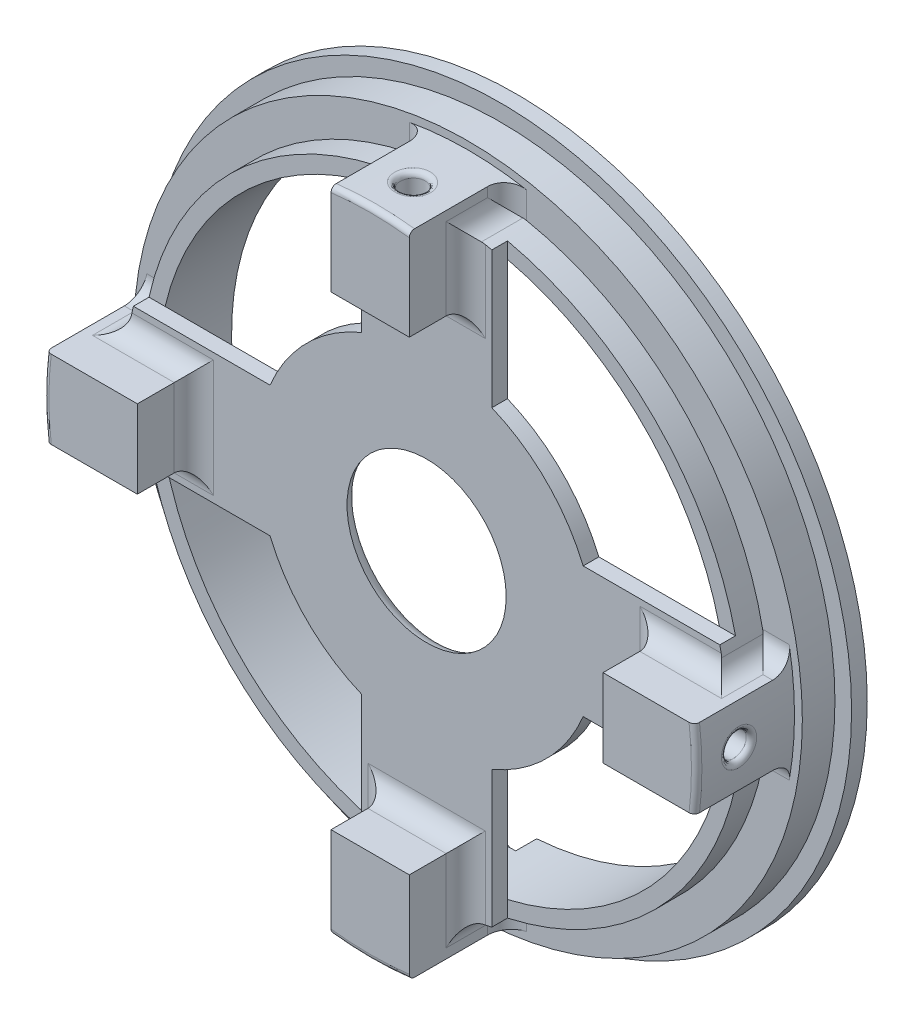
SolidWorks part; units mm, degrees
ref_plane "Front Plane" through (0, 0, 0) normal (0, 0, 1) x (1, 0, 0)
ref_plane "Top Plane" through (0, 0, 0) normal (0, 1, 0) x (1, 0, 0)
ref_plane "Right Plane" through (0, 0, 0) normal (1, 0, 0) x (0, 0, -1)
sketch "Sketch1" plane through (0, 0, 0) normal (0, 0, 1) x (1, 0, 0)
  circle A0 centre (0, 0) radius 53.8 construction
  circle A1 centre (0, 0) radius 53.8
  circle A4 centre (0, 0) radius 43.65
  circle A5 centre (0, 0) radius 43.65
  dimension "D1" = 0.65
extrude "Boss-Extrude1" add sketch "Sketch1" along normal blind 2.4
sketch "Sketch6" plane through (0, 0, 10.2) normal (0, 0, 1) x (1, 0, 0)
  circle A2 centre (0, 0) radius 43.65 construction
  circle A3 centre (0, 0) radius 43.65
extrude "Boss-Extrude4" add sketch "Sketch6" along normal blind 2.4 from offset 1.15 separate body
sketch "Sketch7" plane through (0, 0, 2.4) normal (0, 0, 1) x (1, 0, 0)
  circle A0 centre (0, 0) radius 43.65 construction
  circle A1 centre (0, 0) radius 43.65
extrude "Extrude-Thin2" add sketch "Sketch7" along normal up to surface (11.35 mm away) thin up to face at (43.65, 0, 13.75) thin type one direction wall 2.4
sketch "Sketch9" plane through (0, 0, 13.75) normal (0, 0, 1) x (1, 0, 0)
  circle A2 centre (0, 0) radius 12.2
  circle A3 centre (0, 0) radius 12.2
  dimension "D1" = 0.2
extrude "Cut-Extrude1" cut sketch "Sketch9" against normal up to surface (2.4 mm away) up to face at (43.65, 0, 11.35)
sketch "Sketch10" plane through (0, 0, 13.75) normal (0, 0, 1) x (1, 0, 0)
  line L0 (0, -46.05) -> (0, 46.05) construction
  line L1 (46.05, 0) -> (-46.05, 0) construction
  line L2 (10, -44.9511) -> (10, 44.9511)
  line L3 (44.9511, -10) -> (-44.9511, -10)
  line L4 (44.9511, 10) -> (-44.9511, 10)
  line L5 (-10, -44.9511) -> (-10, 44.9511)
  circle A0 centre (0, 0) radius 46.05 construction
  circle A1 centre (0, 0) radius 46.05
  circle A2 centre (0, 0) radius 26
  point P9 (10, 0)
  point P12 (0, -10)
  circle M7 centre (0, 0) radius 46.05
  dimension "D3" = 52
  dimension "D1" = 10
  dimension "D2" = 10
extrude "Cut-Extrude2" cut sketch "Sketch10" against normal up to surface (2.4 mm away) contours A2 L2 L3 M7 | A2 L3 L5 M7 | A2 L5 L4 M7 | A2 L4 L2 M7 region at (25.3451, -25.3451, 13.75) region at (-25.3451, -25.3451, 13.75) region at (-25.3451, 25.3451, 13.75) region at (25.3451, 25.3451, 13.75) up to face at (12.2, 0, 11.35)
sketch "Sketch8" plane through (0, 0, 2.4) normal (0, 0, 1) x (1, 0, 0)
  circle A2 centre (0, 0) radius 46.05 construction
  circle A3 centre (0, 0) radius 46.05
  circle A6 centre (0, 0) radius 51.25
  circle A7 centre (0, 0) radius 51.25
  dimension "D1" = 2.55
extrude "Boss-Extrude5" add sketch "Sketch8" along normal blind 5
sketch "Sketch12" plane through (0, 0, 7.4) normal (0, 0, 1) x (1, 0, 0)
  line L0 (0, 0) -> (-50.05, 0) construction
  line L1 (-49.6891, -6) -> (-35.6891, -6)
  line L2 (-35.6891, -6) -> (-35.6891, 6)
  line L3 (-49.6891, 6) -> (-35.6891, 6)
  circle A2 centre (0, 0) radius 50.05
  circle A3 centre (0, 0) radius 50.05
  point P8 (-35.6891, 0)
  circle M6 centre (0, 0) radius 46.05
  dimension "D2" = 6
  dimension "D3" = 14
  dimension "D1" = 1.2
extrude "Boss-Extrude6" add sketch "Sketch12" along normal blind 15 contours L2 L0 L1 M6 | L0 L2 L3 M6 | L0 A3 L1 M6 | L0 L3 A3 M6 region at (-40.8049, -2.9808, 7.4) region at (-40.8049, 2.9808, 7.4) region at (-47.9244, -3.0039, 7.4) region at (-47.9244, 3.0039, 7.4)
sketch "Sketch14" plane through (0, 0, 7.4) normal (0, 0, -1) x (-1, 0, 0)
  line L3 (43.2357, 6) -> (35.6891, 6)
  line L4 (35.6891, 6) -> (35.6891, -6)
  line L5 (35.6891, -6) -> (43.2357, -6)
  line L6 (43.2357, 6) -> (35.6891, 6)
  line L7 (35.6891, 6) -> (35.6891, -6)
  line L8 (35.6891, -6) -> (43.2357, -6)
  arc A1 (43.2357, -6) -> (43.2357, 6) centre (0, 0) ccw
  arc A2 (43.2357, -6) -> (43.2357, 6) centre (0, 0) ccw
  dimension "D1" = 0
extrude "Cut-Extrude4" cut sketch "Sketch14" against normal up to surface (3.95 mm away) up to face at (-7.8391, 0, 11.35)
sketch "Sketch13" plane through (-35.6891, 0, 0) normal (1, 0, 0) x (0, 0, -1)
  line L0 (-22.4, -6) -> (-22.4, 6) construction
  circle A0 centre (-15.9, 0) radius 1.9
  point P2 (-22.4, 0)
  dimension "D1" = 3.8
  dimension "D2" = 6.5
extrude "Cut-Extrude3" cut sketch "Sketch13" against normal through all from offset 5 offset against normal yes
fillet "Fillet1" radius 3 7 edges at (-35.6891, 0, 13.75) (-40.6733, -6, 13.75) (-45.6574, -6, 10.575) (-45.6574, 6, 10.575) (-40.6733, 6, 13.75) (-47.6733, -6, 7.4) (-47.6733, 6, 7.4)
fillet "Fillet2" radius 0.8 2 edges at (-50.05, 0, 22.4) (-50.0481, -0.4355, 17.7494)
pattern_circular "CirPattern4" count 4 over 360 about axis through (0, 0, 143.9991) along (0, 0, -1) of "Boss-Extrude6", "Cut-Extrude4", "Cut-Extrude3", "Fillet1", "Fillet2"
sketch "Sketch17" plane through (0, 0, 0) normal (0, 0, -1) x (-1, 0, 0)
  circle A0 centre (0, 0) radius 43.65 construction
  circle A1 centre (0, 0) radius 43.65
  ellipse E0 centre (0, 43) end of major axis (0, 39.2) minor radius 3 (2.9989, 42.8953) -> (-2.9989, 42.8953) ccw construction
  ellipse E1 centre (0, -43) end of major axis (0, -39.2) minor radius 3 (-2.9989, -42.8953) -> (2.9989, -42.8953) ccw construction
  ellipse E2 centre (0, 43) end of major axis (0, 39.2) minor radius 3 (2.9989, 42.8953) -> (-2.9989, 42.8953) ccw
  ellipse E3 centre (0, -43) end of major axis (0, -39.2) minor radius 3 (-2.9989, -42.8953) -> (2.9989, -42.8953) ccw
  spline S0 degree 1 poles (-3.1488, -42.892) (3.1488, -42.892) knots 0 0 1 1 construction
  spline S1 degree 3 poles (-3.1488, -42.892) (-3.1601, -43.4079) (-3.0156, -44.4646) (-2.1068, -46.2652) (0, -47.4065) (2.1068, -46.2652) (3.0156, -44.4646) (3.1601, -43.4079) (3.1488, -42.892) knots 1.54324 1.54324 1.54324 1.54324 1.942828 2.342417 3.141593 3.940769 4.340357 4.739945 4.739945 4.739945 4.739945
  spline S2 degree 1 poles (3.1488, 42.892) (-3.1488, 42.892) knots 0 0 1 1 construction
  spline S3 degree 3 poles (3.1488, 42.892) (3.1601, 43.4079) (3.0156, 44.4646) (2.1068, 46.2652) (0, 47.4065) (-2.1068, 46.2652) (-3.0156, 44.4646) (-3.1601, 43.4079) (-3.1488, 42.892) knots 1.54324 1.54324 1.54324 1.54324 1.942828 2.342417 3.141593 3.940769 4.340357 4.739945 4.739945 4.739945 4.739945
  circle M3 centre (0, 0) radius 43.65
extrude "Cut-Extrude5" cut sketch "Sketch17" against normal blind 3.2 contours E2 M3 | A1 S3 E2 | E3 M3 | A1 S1 E3 M3 region at (-3.0492, 43.6147, 0) region at (0, -46.8789, 0) region at (0, 44.9502, 0) region at (0, -44.9502, 0)
fillet "Fillet3" radius 3 1 edges at (12.2, 0, 11.35)
equation "\"D1@Boss-Extrude1\"=\"Wall thickness@BOX_PLAYERS.Assembly\""
equation "\"D1@Sketch1\"=\"Gap@BOX_PLAYERS.Assembly\"+0.5"
equation "\"D1@Boss-Extrude4\"=\"Wall thickness@BOX_PLAYERS.Assembly\""
equation "\"D19@Boss-Extrude4\"=\"Gap@BOX_PLAYERS.Assembly\"+1"
equation "\"D5@Extrude-Thin2\"=\"Wall thickness@BOX_PLAYERS.Assembly\""
equation "\"D1@Sketch8\"=\"Wall thickness@BOX_PLAYERS.Assembly\"+\"Gap@BOX_PLAYERS.Assembly\""
equation "\"D1@Sketch12\"=\"Body thickening@BOX_PLAYERS.Assembly\""
equation "\"D1@Sketch13\"=\"Sleeve@BOX_PLAYERS.Assembly\""
equation "\"D1@Sketch17\"=\"Gap@BOX_PLAYERS.Assembly\""
